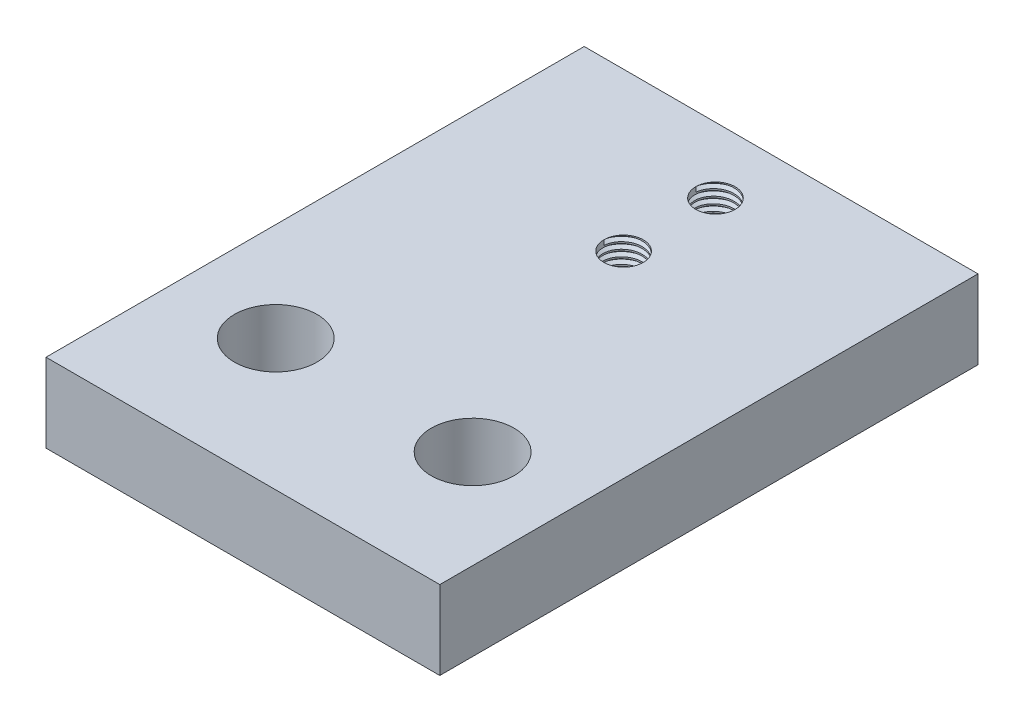
SolidWorks part; units mm, degrees
material "6061-T6 (SS)"
ref_plane "Front Plane" through (0, 0, 0) normal (0, 0, 1) x (1, 0, 0)
ref_plane "Top Plane" through (0, 0, 0) normal (0, 1, 0) x (1, 0, 0)
ref_plane "Right Plane" through (0, 0, 0) normal (1, 0, 0) x (0, 0, -1)
sketch "Sketch1" plane through (0, 0, 0) normal (0, 1, 0) x (1, 0, 0)
  line L0 (-15, 2.5) -> (15, 2.5) construction
  line L1 (-15, 20.5) -> (15, 20.5)
  line L2 (-15, 20.5) -> (-15, -20.5)
  line L3 (-15, -20.5) -> (15, -20.5)
  line L4 (15, 20.5) -> (15, -20.5)
  line L5 (0, 20.5) -> (0, -20.5) construction
  circle A0 centre (0, 15.5) radius 1.5
  circle A1 centre (0, 8.5) radius 1.5
  circle A2 centre (-7.5, -10.5) radius 3.15
  circle A3 centre (7.5, -10.5) radius 3.15
  point P4 (-15, 0)
  point P6 (0, 20.5)
  dimension "D1" = 15
  dimension "D2" = 7
  dimension "D3" = 5
  dimension "D4" = 6
  dimension "D5" = 3
  dimension "D6" = 6.3
  dimension "D7" = 10
  dimension "D8" = 13
  dimension "D9" = 30
extrude "Boss-Extrude1" add sketch "Sketch1" along normal blind 6
thread "Thread1" pitch 0.5 method cut profile "Thread Profile1" start angle 0, offset 0, length 10, pitch 0.5, diameter 3
ref_plane "Plane1" through (-1.5, 6, -15.5) normal (0, 0, 1) x (-1, 0, 0)
sketch "Thread Profile1" plane through (-1.5, 6, -15.5) normal (0, 0, 1) x (-1, 0, 0)
  line L0 (0, 0) -> (0, 0.5) construction
  line L1 (0, 0) -> (0.2706, 0.1562)
  line L2 (0.2706, 0.1562) -> (0.2706, 0.2187)
  line L3 (0.2706, 0.2187) -> (0, 0.375)
  line L4 (0.2706, 0.1875) -> (0, 0.1875) construction
  line L11 (0, 0) -> (0, 0.375)
  point P2 (0, 0)
  dimension "Pitch" = 0.5
  dimension "Profile_Angle" = 60
  dimension "Profile_Land" = 0.0625
  dimension "Profile_Height" = 0.2706
thread "Thread2" pitch 0.5 method cut profile "Thread Profile2" start angle 0, offset 0, length 10, pitch 0.5, diameter 3
ref_plane "Plane2" through (-1.5, 6, -8.5) normal (0, 0, 1) x (-1, 0, 0)
sketch "Thread Profile2" plane through (-1.5, 6, -8.5) normal (0, 0, 1) x (-1, 0, 0)
  line L0 (0, 0) -> (0, 0.5) construction
  line L1 (0, 0) -> (0.2706, 0.1562)
  line L2 (0.2706, 0.1562) -> (0.2706, 0.2187)
  line L3 (0.2706, 0.2187) -> (0, 0.375)
  line L4 (0.2706, 0.1875) -> (0, 0.1875) construction
  line L11 (0, 0) -> (0, 0.375)
  point P2 (0, 0)
  dimension "Pitch" = 0.5
  dimension "Profile_Angle" = 60
  dimension "Profile_Land" = 0.0625
  dimension "Profile_Height" = 0.2706
